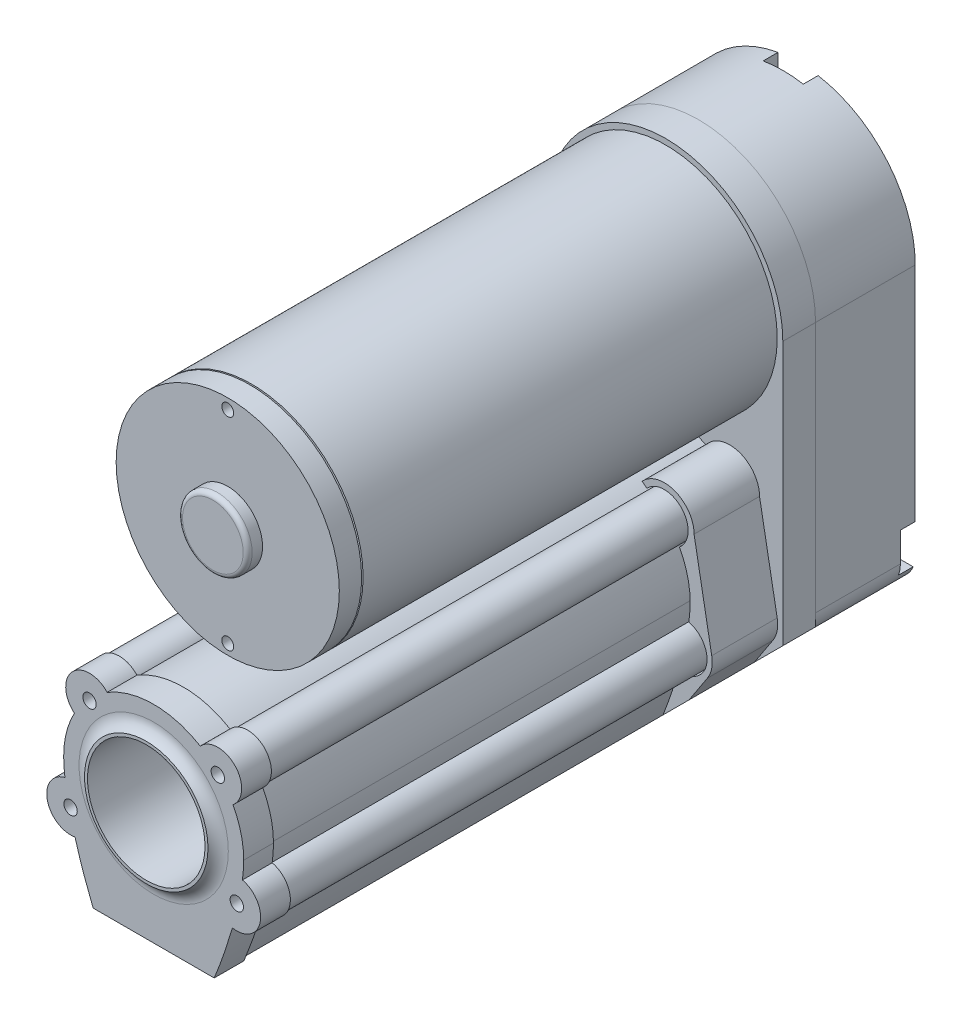
SolidWorks part; units mm, degrees
ref_plane "Front Plane" through (0, 0, 0) normal (0, 0, 1) x (1, 0, 0)
ref_plane "Top Plane" through (0, 0, 0) normal (0, 1, 0) x (1, 0, 0)
ref_plane "Right Plane" through (0, 0, 0) normal (1, 0, 0) x (0, 0, -1)
sketch "Sketch1" plane through (0, 0, 0) normal (0, 0, 1) x (1, 0, 0)
  line L0 (0, 0) -> (0, 55.0037)
  line L1 (0, 0) -> (40.005, 0)
  line L2 (40.005, 0) -> (40.005, 55.0037)
  arc A0 (40.005, 55.0037) -> (0, 55.0037) centre (20.0025, 55.0037) ccw
  dimension "D1" = 75.0062
  dimension "D2" = 40.005
extrude "Boss-Extrude1" add sketch "Sketch1" along normal mid plane 17.018 contours L0 A0 L2 L1
ref_plane "Plane1" through (0, 0, 8.509) normal (0, 0, 1) x (1, 0, 0)
sketch "Sketch5" plane through (0, 0, 8.509) normal (0, 0, 1) x (1, 0, 0)
  line L0 (0, 0) -> (0, 55.0037) construction
  line L1 (0, 0) -> (40.005, 0) construction
  line L2 (40.005, 0) -> (40.005, 55.0037) construction
  line L3 (0, 0) -> (0, 55.0037)
  line L4 (0, 0) -> (40.005, 0)
  line L5 (40.005, 0) -> (40.005, 55.0037)
  arc A0 (40.005, 55.0037) -> (0, 55.0037) centre (20.0025, 55.0037) ccw construction
  arc A1 (40.005, 55.0037) -> (0, 55.0037) centre (20.0025, 55.0037) ccw
extrude "Boss-Extrude3" add sketch "Sketch5" along normal blind 5.588 separate body
fillet "Fillet1" [suppressed] radius 2.54
sketch "Sketch6" plane through (0, 0, 14.097) normal (0, 0, 1) x (1, 0, 0)
  circle A0 centre (20.0025, 55.0037) radius 19.05
  dimension "D1" = 38.1
extrude "Boss-Extrude4" add sketch "Sketch6" along normal blind 70.6882
sketch "Sketch9" plane through (0, 0, -8.509) normal (0, 0, -1) x (-1, 0, 0)
  line L0 (-16.5735, 71.628) -> (-16.5735, 75.184)
  line L1 (-23.4315, 71.628) -> (-23.4315, 75.184)
  line L2 (-23.4315, 75.184) -> (-16.5735, 75.184)
  line L6 (-34.5025, 17.057) -> (-41.6084, 17.057)
  line L8 (-34.5025, 10.199) -> (-41.6084, 10.199)
  line L9 (-41.6084, 17.057) -> (-41.6084, 10.199)
  line L10 (-5.5025, 17.057) -> (2.6376, 17.057)
  line L12 (-5.5025, 10.199) -> (2.6376, 10.199)
  line L13 (2.6376, 17.057) -> (2.6376, 10.199)
  arc A0 (-34.5025, 10.199) -> (-34.5025, 17.057) centre (-34.5025, 13.628) ccw
  arc A1 (-5.5025, 17.057) -> (-5.5025, 10.199) centre (-5.5025, 13.628) ccw
  arc A2 (-23.4315, 71.628) -> (-16.5735, 71.628) centre (-20.0025, 71.628) ccw
  dimension "D1" = 6.858
  dimension "D2" = 6.858
  dimension "D3" = 6.858
  dimension "D5" = 58
  dimension "D6" = 58
  dimension "D4" = 3.556
  dimension "D7" = 29
  dimension "D8" = 14.5
extrude "Cut-Extrude1" cut sketch "Sketch9" against normal blind 2.54
sketch "Sketch10" plane through (0, 0, 14.097) normal (0, 0, 1) x (1, 0, 0)
  line L0 (20.0025, -8.5483) -> (20.0025, 28.86) construction
  line L1 (9.8425, 0) -> (30.1625, 0)
  line L2 (0, 0) -> (40.005, 0) construction
  line L3 (0, 55.0037) -> (0, 0) construction
  circle A0 centre (20.0025, 19.685) radius 10.033
  arc A1 (35.1155, 19.685) -> (33.2111, 27.029) centre (20.0025, 19.685) ccw
  arc A2 (33.2556, 9.0067) -> (34.8711, 16.4489) centre (34.1913, 12.7) ccw
  arc A3 (33.2111, 27.029) -> (28.0023, 32.5071) centre (30.9547, 30.099) ccw
  arc A4 (6.7494, 9.0067) -> (5.1339, 16.4489) centre (5.8137, 12.7) cw
  arc A5 (6.7939, 27.029) -> (12.0027, 32.5071) centre (9.0503, 30.099) cw
  arc A6 (28.0023, 32.5071) -> (12.0027, 32.5071) centre (20.0025, 19.685) ccw
  arc A7 (6.7939, 27.029) -> (4.8895, 19.685) centre (20.0025, 19.685) ccw
  spline S0 degree 3 poles (30.1625, 0) (31.2263, 2.6097) (32.3487, 5.7927) (33.2556, 9.0067) knots 0 0 0 0 0.457098 0.457098 0.457098 0.457098
  spline S1 degree 3 poles (9.8425, 0) (8.7787, 2.6097) (7.6563, 5.7927) (6.7494, 9.0067) knots 0 0 0 0 0.457098 0.457098 0.457098 0.457098
  spline S2 degree 3 poles (5.1339, 16.4489) (4.9872, 17.5419) (4.8946, 18.6236) (4.8895, 19.6345) (4.8895, 19.685) knots 0.819985 0.819985 0.819985 0.819985 0.990999 1 1 1 1
  spline S3 degree 3 poles (34.8711, 16.4489) (35.0178, 17.5419) (35.1104, 18.6236) (35.1155, 19.6345) (35.1155, 19.685) knots 0.819985 0.819985 0.819985 0.819985 0.990999 1 1 1 1
  point P14 (20.0025, 0)
  dimension "D2" = 20.066
  dimension "D4" = 30.226
  dimension "D3" = 34.798
  dimension "D5" = 7.7096
  dimension "D9" = 7.62
  dimension "D10" = 34.1913
  dimension "D1" = 10.16
  dimension "D6" = 5.8489
  dimension "D7" = 12.7
  dimension "D8" = 30.099
  dimension "D11" = 5.1339
  dimension "D12" = 6.7494
  dimension "D13" = 32.2954
extrude "Boss-Extrude6" add sketch "Sketch10" along normal blind 82.313 contours A0 | A6 A5 A7 S2 A4 S1 L1 S0 A2 S3 A1 A3
sketch "Sketch12" plane through (0, 0, 96.41) normal (0, 0, 1) x (1, 0, 0)
  line L2 (9.6717, -0.254) -> (30.3333, -0.254)
  line L3 (9.6717, -0.254) -> (30.3333, -0.254)
  circle A7 centre (20.0025, 19.685) radius 10.033 construction
  circle A8 centre (20.0025, 19.685) radius 10.033
  arc A14 (33.5376, 26.9614) -> (27.9511, 32.8366) centre (30.9547, 30.099) ccw
  arc A15 (27.9511, 32.8366) -> (12.0539, 32.8366) centre (20.0025, 19.685) ccw
  arc A16 (12.0539, 32.8366) -> (6.4674, 26.9614) centre (9.0503, 30.099) ccw
  arc A17 (6.4674, 26.9614) -> (4.6355, 19.685) centre (20.0025, 19.685) ccw
  arc A18 (4.8516, 16.6485) -> (6.5704, 8.7071) centre (5.8137, 12.7) ccw
  arc A19 (33.4346, 8.7071) -> (35.1534, 16.6485) centre (34.1913, 12.7) ccw
  arc A20 (35.3695, 19.685) -> (33.5376, 26.9614) centre (20.0025, 19.685) ccw
  arc A21 (33.5376, 26.9614) -> (27.9511, 32.8366) centre (30.9547, 30.099) ccw
  arc A22 (27.9511, 32.8366) -> (12.0539, 32.8366) centre (20.0025, 19.685) ccw
  arc A23 (12.0539, 32.8366) -> (6.4674, 26.9614) centre (9.0503, 30.099) ccw
  arc A24 (6.4674, 26.9614) -> (4.6355, 19.685) centre (20.0025, 19.685) ccw
  arc A25 (4.8516, 16.6485) -> (6.5704, 8.7071) centre (5.8137, 12.7) ccw
  arc A26 (33.4346, 8.7071) -> (35.1534, 16.6485) centre (34.1913, 12.7) ccw
  arc A27 (35.3695, 19.685) -> (33.5376, 26.9614) centre (20.0025, 19.685) ccw
  spline S8 degree 3 poles (3001.0592, -87.1889) (-3016.0112, 306.3589) (3025.5743, -309.9621) (-2987.7512, 210.2659) knots -38.253728 -38.253728 -38.253728 -38.253728 41.995553 41.995553 41.995553 41.995553 only from (4.6355, 19.685) to (4.8516, 16.6485)
  spline S9 degree 3 poles (2942.8657, 550.3804) (134.5674, 290.2857) (-29.5411, 112.7018) (8.2588, 3.4372) (8.527, 2.6934) (37.4017, -74.0852) (188.1428, -103.8588) (-2695.5332, -1282.9861) knots -35.807014 -35.807014 -35.807014 -35.807014 0.5 0.5 0.75 0.75 26.443477 26.443477 26.443477 26.443477 only from (6.5704, 8.7071) to (9.6717, -0.254)
  spline S10 degree 3 poles (2721.4691, -1312.3327) (-147.2993, -102.4615) (2.6344, -74.0034) (31.4782, 2.6939) (31.7464, 3.4377) (69.6516, 113.0092) (-96.4312, 288.2244) (-2785.7874, 1000.652) knots -25.408422 -25.408422 -25.408422 -25.408422 0.25 0.25 0.5 0.5 36.909627 36.909627 36.909627 36.909627 only from (30.3333, -0.254) to (33.4346, 8.7071)
  spline S11 degree 3 poles (3029.4649, 182.1475) (-2986.9479, -283.6551) (3057.0444, 281.6839) (-2961.724, -64.0429) knots -41.009223 -41.009223 -41.009223 -41.009223 39.261525 39.261525 39.261525 39.261525 only from (35.1534, 16.6485) to (35.3695, 19.685)
  spline S12 degree 3 poles (4.6355, 19.685) (4.6355, 18.6694) (4.7231, 17.6558) (4.8516, 16.6485) knots 0 0 0 0 1 1 1 1
  spline S13 degree 3 poles (6.5704, 8.7071) (7.0045, 7.1864) (7.4833, 5.6789) (8.2588, 3.4372) (8.527, 2.6934) (9.0835, 1.2137) (9.3733, 0.4782) (9.6717, -0.254) knots 0 0 0 0 0.5 0.5 0.75 0.75 1 1 1 1
  spline S14 degree 3 poles (30.3333, -0.254) (30.6317, 0.4782) (30.9216, 1.2138) (31.4782, 2.6939) (31.7464, 3.4377) (32.5219, 5.6794) (33.0005, 7.1864) (33.4346, 8.7071) knots 0 0 0 0 0.25 0.25 0.5 0.5 1 1 1 1
  spline S15 degree 3 poles (35.1534, 16.6485) (35.2819, 17.6559) (35.3695, 18.6693) (35.3695, 19.685) knots 0 0 0 0 1 1 1 1
  dimension "D1" = 0.254
extrude "Boss-Extrude7" add sketch "Sketch12" along normal blind 5.08
sketch "Sketch14" plane through (0, 0, 101.49) normal (0, 0, 1) x (1, 0, 0)
  circle A0 centre (20.0025, 19.685) radius 10.033 construction
  circle A1 centre (20.0025, 19.685) radius 10.033
  circle A2 centre (20.0025, 19.685) radius 10.541
  dimension "D1" = 0.508
extrude "Boss-Extrude8" add sketch "Sketch14" along normal blind 1.27
fillet "Fillet2" radius 2.54 1 edges at (30.5435, 19.685, 101.49)
sketch "Sketch16" plane through (0, 0, -5.969) normal (0, 0, -1) x (-1, 0, 0)
  circle A0 centre (-34.5025, 13.628) radius 1.143
  circle A1 centre (-5.5025, 13.628) radius 1.143
  circle A2 centre (-20.0025, 71.628) radius 1.143
  dimension "D1" = 2.286
extrude "Cut-Extrude2" cut sketch "Sketch16" against normal blind 17.78
sketch "Sketch17" plane through (0, 0, 101.49) normal (0, 0, 1) x (1, 0, 0)
  circle A0 centre (30.9547, 30.099) radius 1.143
  circle A1 centre (34.1913, 12.7) radius 1.143
  circle A2 centre (5.8137, 12.7) radius 1.143
  circle A3 centre (9.0503, 30.099) radius 1.143
  dimension "D1" = 2.286
extrude "Cut-Extrude3" cut sketch "Sketch17" against normal blind 12.7
ref_plane "Plane3" through (0, 0, 85.0392) normal (0, 0, 1) x (1, 0, 0)
sketch "Sketch19" plane through (0, 0, 85.0392) normal (0, 0, 1) x (1, 0, 0)
  circle A0 centre (20.0025, 55.0037) radius 19.05 construction
  circle A1 centre (20.0025, 55.0037) radius 19.05
extrude "Boss-Extrude9" add sketch "Sketch19" along normal blind 3.81 separate body
sketch "Sketch20" plane through (0, 0, 88.8492) normal (0, 0, 1) x (1, 0, 0)
  circle A0 centre (20.0025, 55.0037) radius 5.9436
  dimension "D1" = 11.8872
extrude "Boss-Extrude10" add sketch "Sketch20" along normal blind 2.54
fillet "Fillet4" radius 0.762 1 edges at (25.9461, 55.0037, 91.3892)
ref_plane "Plane4" through (20.0025, 0, 0) normal (1, 0, 0) x (0, 0, -1)
sketch "Sketch24" plane through (0, 0, 88.8492) normal (0, 0, 1) x (1, 0, 0)
  line L0 (20.0025, 77.5374) -> (20.0025, 33.7577) construction
  line L1 (-2.5816, 55.0037) -> (44.7592, 55.0037) construction
  circle A0 centre (20.0025, 72.2757) radius 1.016
  circle A1 centre (20.0025, 37.7317) radius 1.016
  dimension "D1" = 2.032
  dimension "D2" = 17.272
extrude "Cut-Extrude6" cut sketch "Sketch24" against normal blind 12.7
sketch "Sketch25" plane through (0, 0, 14.097) normal (0, 0, 1) x (1, 0, 0)
  line L2 (30.4367, 0) -> (31.7791, 0)
  line L3 (8.2259, 0) -> (9.5683, 0)
  line L5 (0, 0) -> (9.8425, 0) construction
  line L6 (34.8708, 16.4453) -> (35.1155, 19.685) construction
  line L7 (36.2107, 17.3226) -> (36.3854, 19.6361) construction
  line L8 (36.0347, 30.099) -> (39.048, 13.6393)
  line L9 (38.2986, 9.938) -> (31.7791, 0)
  line L10 (5.1342, 16.4453) -> (4.8886, 19.6965) construction
  line L11 (3.7943, 17.3226) -> (3.6187, 19.6481) construction
  line L12 (20.0025, 23.731) -> (20.0025, -4.7422) construction
  line L13 (1.7064, 9.938) -> (8.2259, 0)
  line L14 (3.9703, 30.099) -> (0.957, 13.6393)
  line L15 (9.8425, 0) -> (6.752, 8.999) construction
  line L16 (8.0635, 1.27) -> (5.8742, 7.6451) construction
  line L17 (0, 1.27) -> (8.0635, 1.27) construction
  line L18 (30.824, 0) -> (40.005, 0) construction
  line L19 (32.4823, 1.27) -> (40.005, 1.27) construction
  line L20 (30.824, 0) -> (33.253, 8.999) construction
  line L21 (32.4823, 1.27) -> (34.2034, 7.6468) construction
  line L23 (12.0329, 32.8595) -> (12.8214, 33.5026)
  line L24 (27.9721, 32.8595) -> (27.1836, 33.5026)
  arc A6 (35.1418, 16.6513) -> (33.4346, 8.7071) centre (34.1913, 12.7) cw
  arc A12 (38.2986, 9.938) -> (39.048, 13.6393) centre (34.0511, 12.7245) ccw
  arc A13 (12.9869, 33.3098) -> (5.2238, 26.7576) centre (9.0503, 30.099) ccw construction
  arc A14 (36.0347, 30.099) -> (27.1836, 33.5026) centre (30.9547, 30.099) ccw
  arc A15 (12.8214, 33.5026) -> (3.9703, 30.099) centre (9.0503, 30.099) ccw
  arc A16 (3.7943, 17.3226) -> (5.8742, 7.6451) centre (5.9539, 12.7245) ccw construction
  arc A17 (0.957, 13.6393) -> (1.7064, 9.938) centre (5.9539, 12.7245) ccw
  arc A18 (36.3854, 19.6361) -> (34.7805, 26.7569) centre (20.0025, 19.685) ccw construction
  arc A19 (5.2238, 26.7576) -> (3.6187, 19.6481) centre (20.0025, 19.685) ccw construction
  arc A20 (34.2034, 7.6468) -> (36.2107, 17.3226) centre (34.0511, 12.7245) ccw construction
  arc A21 (34.7805, 26.7569) -> (27.0181, 33.3098) centre (30.9547, 30.099) ccw construction
  arc A22 (4.8639, 16.6514) -> (6.5704, 8.7071) centre (5.8137, 12.7) ccw
  arc A23 (6.4667, 26.9619) -> (4.6346, 19.687) centre (20.0025, 19.685) ccw
  arc A24 (12.0329, 32.8595) -> (6.4667, 26.9619) centre (9.0503, 30.099) ccw
  arc A26 (35.3695, 19.6754) -> (33.5376, 26.9614) centre (20.0025, 19.685) ccw
  arc A27 (33.5376, 26.9614) -> (27.9721, 32.8595) centre (30.9547, 30.099) ccw
  arc A28 (12.0027, 32.5071) -> (6.7932, 27.0295) centre (9.0503, 30.099) ccw construction
  arc A29 (6.7932, 27.0295) -> (4.8886, 19.6965) centre (20.0025, 19.685) ccw construction
  arc A30 (5.1342, 16.4453) -> (6.752, 8.999) centre (5.9539, 12.7245) ccw construction
  arc A31 (33.253, 8.999) -> (34.8708, 16.4453) centre (34.0511, 12.7245) ccw construction
  arc A32 (35.1155, 19.685) -> (33.2111, 27.029) centre (20.0025, 19.685) ccw construction
  arc A33 (33.2111, 27.029) -> (28.0023, 32.5071) centre (30.9547, 30.099) ccw construction
  spline S4 degree 3 poles (30.4367, 0) (30.5562, 0.2942) (30.8018, 0.9102) (31.3182, 2.2541) (31.9744, 4.0657) (32.736, 6.3526) (33.2106, 7.9226) (33.4346, 8.7071) knots 0.00546 0.00546 0.00546 0.00546 0.055775 0.111549 0.223098 0.334648 0.446197 0.446197 0.446197 0.446197
  spline S10 degree 3 poles (9.5683, 0) (9.4488, 0.2942) (9.2032, 0.9102) (8.6868, 2.2541) (8.0306, 4.0657) (7.269, 6.3526) (6.7944, 7.9226) (6.5704, 8.7071) knots 0.00546 0.00546 0.00546 0.00546 0.055775 0.111549 0.223098 0.334648 0.446197 0.446197 0.446197 0.446197
  spline S11 degree 3 poles (4.8639, 16.6514) (4.7954, 17.1705) (4.68, 18.2435) (4.6368, 19.1953) (4.6346, 19.687) knots 0.832123 0.832123 0.832123 0.832123 0.916061 1 1 1 1
  spline S15 degree 3 poles (35.1418, 16.6513) (35.2096, 17.1667) (35.3243, 18.2354) (35.3674, 19.1837) (35.3695, 19.6754) knots 0.832741 0.832741 0.832741 0.832741 0.916061 1 1 1 1
  dimension "D1" = 1.27
extrude "Boss-Extrude12" add sketch "Sketch25" along normal blind 11.176
chamfer "Chamfer1" distance 10 angle 45 2 edges at (0, 0, 0) (40.005, 0, 0)
chamfer "Chamfer2" distance 10 angle 45 2 edges at (0, 0, 11.303) (40.005, 0, 11.303)
fillet "Fillet5" radius 5 4 edges at (0, 10, 0) (10, 0, 0) (40.005, 10, 0) (30.005, 0, 0)
